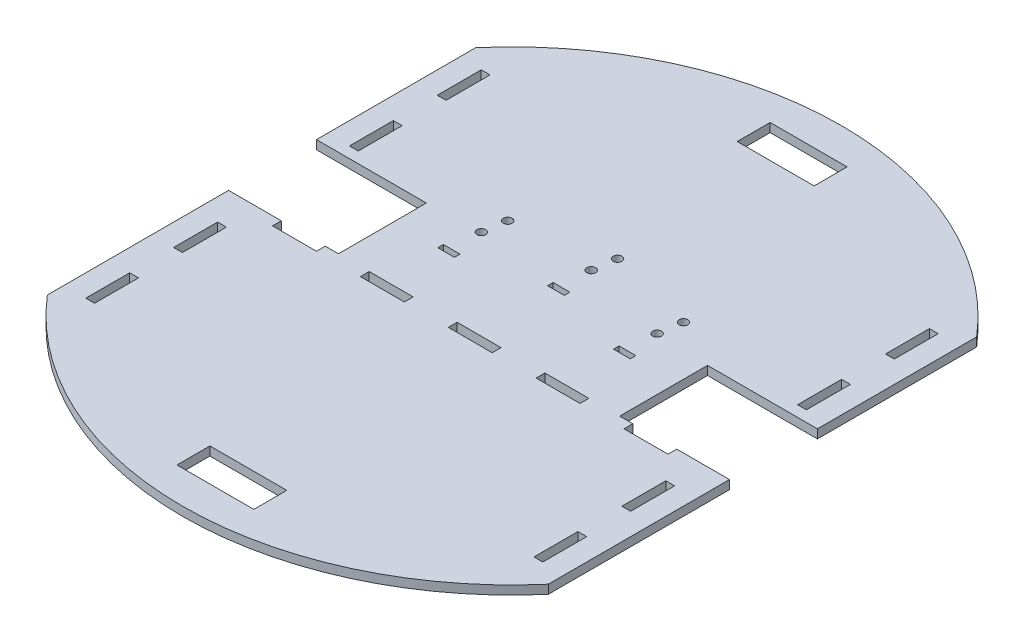
SolidWorks part; units mm, degrees
ref_plane "Přední rovina" through (0, 0, 0) normal (0, 0, 1) x (1, 0, 0)
ref_plane "Horní rovina" through (0, 0, 0) normal (0, 1, 0) x (1, 0, 0)
ref_plane "Pravá rovina" through (0, 0, 0) normal (1, 0, 0) x (0, 0, -1)
sketch "Skica1" plane through (0, 0, 0) normal (0, 1, 0) x (1, 0, 0)
  line L0 (-150, 0) -> (150, 0)
  line L9 (174, -97.4885) -> (114, -97.4885)
  line L10 (-174, 97.4885) -> (-114, 97.4885)
  line L17 (-100, -90) -> (-104, -90)
  line L18 (-100, -90) -> (-100, -70)
  line L19 (-100, -70) -> (-104, -70)
  line L20 (-104, -90) -> (-104, -70)
  line L21 (-100, -50) -> (-104, -50)
  line L22 (-100, -50) -> (-100, -30)
  line L23 (-100, -30) -> (-104, -30)
  line L24 (-104, -50) -> (-104, -30)
  line L25 (0, -150) -> (0, 150)
  line L26 (-100, 30) -> (-104, 30)
  line L27 (-104, 50) -> (-104, 30)
  line L28 (-100, 50) -> (-104, 50)
  line L29 (-100, 50) -> (-100, 30)
  line L30 (-100, 70) -> (-104, 70)
  line L31 (-104, 90) -> (-104, 70)
  line L32 (-100, 90) -> (-104, 90)
  line L33 (-100, 90) -> (-100, 70)
  line L36 (100, 90) -> (100, 70)
  line L37 (100, 90) -> (104, 90)
  line L38 (104, 90) -> (104, 70)
  line L39 (100, 70) -> (104, 70)
  line L40 (100, 50) -> (100, 30)
  line L41 (100, 50) -> (104, 50)
  line L42 (104, 50) -> (104, 30)
  line L43 (100, 30) -> (104, 30)
  line L44 (100, -30) -> (104, -30)
  line L45 (104, -50) -> (104, -30)
  line L46 (100, -50) -> (104, -50)
  line L47 (100, -50) -> (100, -30)
  line L48 (100, -70) -> (104, -70)
  line L49 (104, -90) -> (104, -70)
  line L50 (100, -90) -> (104, -90)
  line L51 (100, -90) -> (100, -70)
  line L52 (-3.81, 22.54) -> (3.81, 22.54)
  line L57 (-3.81, 22.54) -> (-3.81, 20)
  line L58 (-3.81, 20) -> (3.81, 20)
  line L59 (3.81, 22.54) -> (3.81, 20)
  line L60 (-43.81, 10) -> (-36.19, 10)
  line L61 (-43.81, 10) -> (-43.81, 12.54)
  line L62 (-43.81, 12.54) -> (-36.19, 12.54)
  line L63 (-36.19, 10) -> (-36.19, 12.54)
  line L64 (43.81, 10) -> (43.81, 12.54)
  line L65 (43.81, 12.54) -> (36.19, 12.54)
  line L66 (36.19, 10) -> (36.19, 12.54)
  line L67 (43.81, 10) -> (36.19, 10)
  line L80 (-40, 12.54) -> (-40, 26.04)
  line L81 (64, 25) -> (114, 25)
  line L82 (40, 12.54) -> (40, 26.04)
  line L83 (-64, -15) -> (-114, -15)
  line L85 (50, -19) -> (30, -19)
  line L86 (-90, -15) -> (-70, -15)
  line L87 (-90, -15) -> (-90, -19)
  line L88 (-90, -19) -> (-70, -19)
  line L89 (-70, -15) -> (-70, -19)
  line L90 (-50, -15) -> (-30, -15)
  line L91 (-50, -15) -> (-50, -19)
  line L92 (-50, -19) -> (-30, -19)
  line L93 (-30, -15) -> (-30, -19)
  line L94 (-10, -15) -> (10, -15)
  line L95 (-10, -15) -> (-10, -19)
  line L96 (-10, -19) -> (10, -19)
  line L97 (10, -15) -> (10, -19)
  line L98 (30, -15) -> (30, -19)
  line L99 (50, -15) -> (30, -15)
  line L100 (50, -15) -> (50, -19)
  line L101 (90, -19) -> (70, -19)
  line L102 (70, -15) -> (70, -19)
  line L103 (90, -15) -> (70, -15)
  line L104 (90, -15) -> (90, -19)
  line L118 (-17.5, -135) -> (17.5, -135)
  line L119 (-17.5, -135) -> (-17.5, -120)
  line L120 (-17.5, -120) -> (17.5, -120)
  line L121 (17.5, -135) -> (17.5, -120)
  line L122 (-17.5, -135) -> (17.5, -120) construction
  line L123 (-17.5, -120) -> (17.5, -135) construction
  line L124 (-17.5, 120) -> (17.5, 120)
  line L125 (17.5, 135) -> (17.5, 120)
  line L126 (-17.5, 135) -> (17.5, 135)
  line L127 (-17.5, 135) -> (-17.5, 120)
  line L128 (-174, 97.4885) -> (-174, -97.4885)
  line L129 (-174, -97.4885) -> (-114, -97.4885)
  line L130 (-114, 97.4885) -> (-114, -97.4885)
  line L131 (-174, 97.4885) -> (-114, -97.4885) construction
  line L132 (-174, -97.4885) -> (-114, 97.4885) construction
  line L133 (114, 97.4885) -> (114, -97.4885)
  line L134 (174, 97.4885) -> (114, 97.4885)
  line L135 (174, 97.4885) -> (174, -97.4885)
  line L136 (-64, -15) -> (-64, 25)
  line L137 (-64, 25) -> (-114, 25)
  line L138 (-114, -15) -> (-114, 25)
  line L139 (114, -15) -> (114, 25)
  line L140 (64, -15) -> (114, -15)
  line L141 (64, -15) -> (64, 25)
  circle A0 centre (0, 0) radius 150
  circle A1 centre (0, 36.04) radius 2
  circle A2 centre (1.5, 46.54) radius 2
  circle A4 centre (40, 26.04) radius 2
  circle A5 centre (41.5, 36.54) radius 2
  circle A7 centre (-40, 26.04) radius 2
  circle A8 centre (-38.5, 36.54) radius 2
  point P2 (-150, 0)
  point P3 (97.9359, -15)
  point P4 (-144, 0)
  point P7 (0, 0)
  point P8 (150, 0)
  point P10 (0, 0)
  point P11 (0, 0)
  point P17 (-102, -90)
  point P71 (-40, 12.54)
  point P72 (-100, 96.3646)
  point P73 (100, 60.0206)
  point P127 (0, -127.5)
  dimension "D1" = 300
  dimension "D26" = 4
  dimension "D28" = 4
  dimension "D31" = 10
  dimension "D32" = 4
  dimension "D35" = 4
  dimension "D36" = 4
  dimension "D37" = 4
  dimension "D38" = 4
  dimension "D39" = 4
  dimension "D40" = 4
  dimension "D4" = 20
  dimension "D5" = 20
  dimension "D7" = 20
  dimension "D8" = 30
  dimension "D9" = 4
  dimension "D10" = 20
  dimension "D11" = 7.62
  dimension "D12" = 2.54
  dimension "D13" = 3.81
  dimension "D14" = 20
  dimension "D15" = 7.62
  dimension "D16" = 2.54
  dimension "D17" = 40
  dimension "D18" = 20
  dimension "D19" = 10
  dimension "D20" = 20
  dimension "D21" = 4
  dimension "D22" = 40
  dimension "D23" = 50
  dimension "D24" = 50
  dimension "D25" = 90
  dimension "D27" = 13.5
  dimension "D29" = 24
  dimension "D30" = 1.5
  dimension "D33" = 13.5
  dimension "D34" = 100
  dimension "D41" = 1.5
  dimension "D42" = 24
  dimension "D43" = 25
  dimension "D44" = 24
  dimension "D46" = 13.5
  dimension "D49" = 24
  dimension "D50" = 1.5
  dimension "D53" = 20
  dimension "D54" = 20
  dimension "D55" = 20
  dimension "D57" = 20
  dimension "D58" = 20
  dimension "D60" = 35
  dimension "D61" = 15
  dimension "D62" = 135
  dimension "D64" = 60
extrude "Přidat vysunutím1" add sketch "Skica1" along normal blind 4 contours L130 A0 L25 L118 L119 L120 L96 L95 L94 L0 L136 L83 L89 L88 L87 L90 L93 L92 L91 L21 L24 L23 L22 L17 L20 L19 L18 | L25 A0 L133 L140 L104 L101 L102 L141 L0 L94 L97 L96 L120 L121 L118 L99 L100 L85 L98 L50 L51 L48 L49 L46 L47 L44 L45 | A2 L25 A1 L52 L59 L58 L0 L141 L81 L133 A0 L126 L125 L124 A5 A4 L65 L64 L67 L66 L39 L36 L37 L38 L43 L40 L41 L42 | A2 L25 L124 L127 L126 A0 L130 L137 L136 L0 L58 L57 L52 A1 A8 A7 L62 L63 L60 L61 L32 L33 L30 L31 L28 L29 L26 L27 region at (-50.572, 0, -72.0639) region at (-51.8824, 0, 70.7714) region at (50.608, 0, -72.0842) region at (51.8824, 0, 70.7714)
